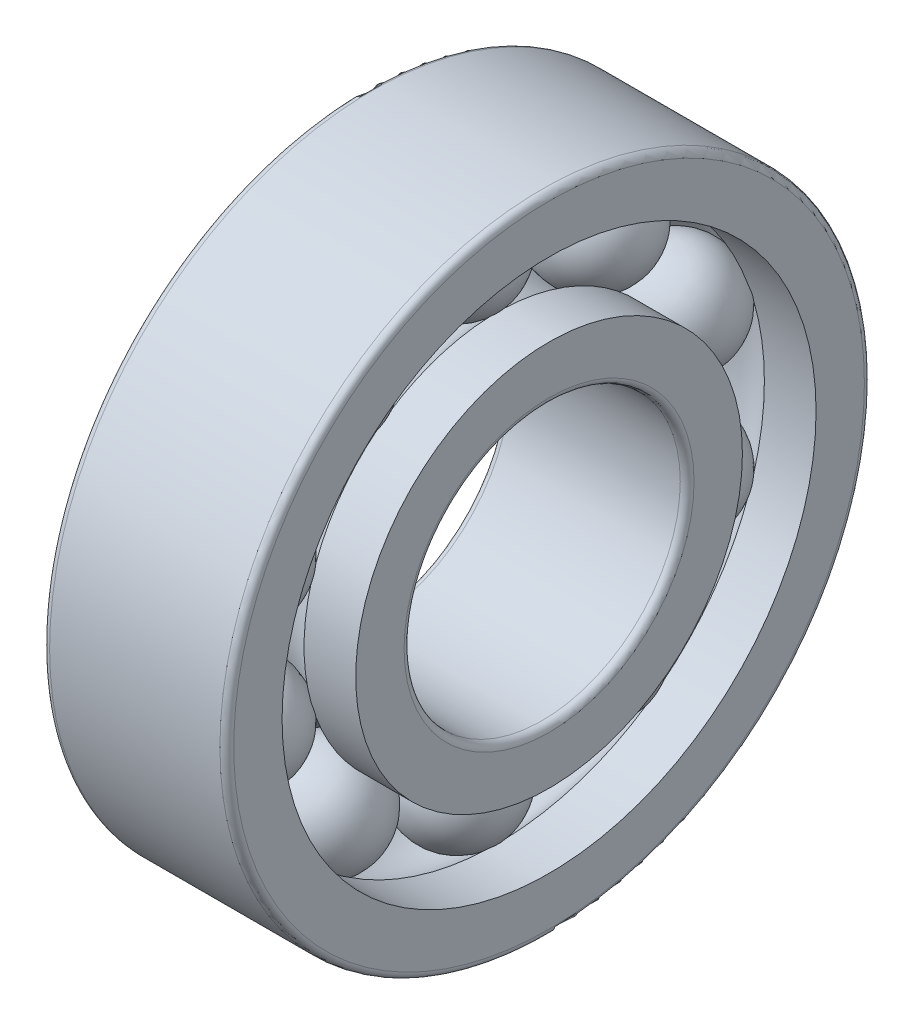
SolidWorks part; units mm, degrees
ref_plane "Plane1" through (0, 0, 0) normal (0, 0, 1) x (1, 0, 0)
ref_plane "Plane2" through (0, 0, 0) normal (0, 1, 0) x (1, 0, 0)
ref_plane "Plane3" through (0, 0, 0) normal (1, 0, 0) x (0, 0, -1)
sketch "Clipboard" plane through (0, 0, 0) normal (0, 0, 1) x (1, 0, 0)
  line L0 (-10, 0) -> (10, 0) construction
  line L1 (0, 0) -> (22.021, -3.8829)
  line L2 (0, 0) -> (9.8481, 1.7365)
  line L3 (0, 0) -> (22.021, -3.8829)
  line L4 (0, 0) -> (-22.3573, -0.3902)
  dimension "BallCLRad" = 10
sketch "CagSpiSke" plane through (0, 0, 0) normal (0, 0, 1) x (1, 0, 0)
  line L0 (0.24, 9.6) -> (0.24, 10.4)
  line L1 (0.24, 10.4) -> (-0.24, 10.4)
  line L2 (-0.24, 10.4) -> (-0.24, 9.6)
  line L3 (-0.24, 9.6) -> (0.24, 9.6)
  line L4 (-20.6375, 0) -> (20.6375, 0) construction
  line L5 (0, 0) -> (0, 23.7692) construction
  dimension "OD" = 20.8
  dimension "ID" = 19.2
revolve "CageSpine" add sketch "CagSpiSke" angle 0.001 about L4 reverse direction yes
ref_axis "Axis1" through (-50, 0, 0) along (1, 0, 0)
sketch "CagBalSke" plane through (0, 0, 0) normal (0, 0, 1) x (1, 0, 0)
  line L0 (-2.64, 10) -> (2.64, 10)
  line L1 (-1.905, 10) -> (1.905, 10) construction
  line L2 (-10, 0) -> (10, 0) construction
  line L3 (0, 0) -> (0, 24) construction
  arc A0 (2.64, 10) -> (-2.64, 10) centre (0, 10) cw
  dimension "BallCLRad" = 10
revolve "CageBall" [suppressed] add sketch "CagBalSke" angle 360 about L1 reverse direction yes
pattern_circular "CageBalls" [suppressed] count 10 every 36 about axis through (-50, 0, 0) along (1, 0, 0)
sketch "CagTrmODSke" plane through (0, 0, 0) normal (0, 0, 1) x (1, 0, 0)
  line L0 (2.641, 10.4) -> (2.641, 12.641)
  line L1 (2.641, 12.641) -> (-2.641, 12.641)
  line L2 (-2.641, 12.641) -> (-2.641, 10.4)
  line L3 (-2.641, 10.4) -> (2.641, 10.4)
  line L4 (-20.6375, 0) -> (20.6375, 0) construction
  line L5 (0, 0) -> (0, 25) construction
  dimension "Width" = 5.282
  dimension "ID" = 20.8
  dimension "OD" = 25.282
revolve "CageTrimOD" [suppressed] cut sketch "CagTrmODSke" angle 360 about L4 reverse direction yes
sketch "CagTrmIDSke" plane through (0, 0, 0) normal (0, 0, 1) x (1, 0, 0)
  line L0 (2.641, 7.361) -> (2.641, 9.6)
  line L1 (2.641, 9.6) -> (-2.641, 9.6)
  line L2 (-2.641, 9.6) -> (-2.641, 7.361)
  line L3 (-2.641, 7.361) -> (2.641, 7.361)
  line L4 (-20.6375, 0) -> (20.6375, 0) construction
  line L5 (0, 0) -> (0, 25) construction
  dimension "Width" = 5.282
  dimension "ID" = 14.722
  dimension "OD" = 19.2
revolve "CageTrimID" [suppressed] cut sketch "CagTrmIDSke" angle 360 about L4 reverse direction yes
sketch "BalSimSke" plane through (0, 0, 0) normal (0, 0, 1) x (1, 0, 0)
  line L0 (-10, 0) -> (10, 0) construction
  line L1 (-10, 10) -> (10, 10) construction
  line L2 (0, 0) -> (0, 23) construction
  circle A0 centre (0, 10) radius 2.4
  dimension "BallCLRad" = 10
  dimension "Ball_diameter" = 4.8
revolve "BallsSimplified" [suppressed] add sketch "BalSimSke" angle 360 about L0
sketch "BalDetSke" plane through (0, 0, 0) normal (0, 0, 1) x (1, 0, 0)
  line L0 (-2.4, 10) -> (2.4, 10)
  line L1 (-1.905, 10) -> (1.905, 10) construction
  line L2 (0, 0) -> (0, 25) construction
  arc A0 (2.4, 10) -> (-2.4, 10) centre (0, 10) cw
  dimension "BallCLRad" = 10
  dimension "Ball_diameter" = 4.8
revolve "BallDetailed" add sketch "BalDetSke" angle 360 about L1 reverse direction yes
sketch "InnRacSke" plane through (0, 0, 0) normal (0, 0, 1) x (1, 0, 0)
  line L0 (-1.7552, 8.4) -> (-4, 8.4)
  line L1 (-4, 8.4) -> (-4, 6.3)
  line L2 (-3.7, 6) -> (3.7, 6)
  line L3 (4, 6.3) -> (4, 8.4)
  line L4 (4, 8.4) -> (1.7552, 8.4)
  line L5 (-20.6375, 0) -> (20.6375, 0) construction
  line L6 (0, 0) -> (0, 30) construction
  arc A0 (-4, 6.3) -> (-3.7, 6) centre (-3.7, 6.3) ccw
  arc A1 (3.7, 6) -> (4, 6.3) centre (3.7, 6.3) ccw
  arc A2 (1.7552, 8.4) -> (-1.7552, 8.4) centre (0, 10) cw
  dimension "BallCLRad" = 10
  dimension "Fillet_radius" = 0.3
  dimension "Ball_diameter" = 4.75
  dimension "ID" = 12
  dimension "OD" = 16.8
  dimension "Width" = 8
revolve "InnerRace" add sketch "InnRacSke" angle 360 about L5 reverse direction yes
sketch "OutRacSke" plane through (0, 0, 0) normal (0, 0, 1) x (1, 0, 0)
  line L0 (-1.7552, 11.6) -> (-4, 11.6)
  line L1 (-4, 11.6) -> (-4, 13.7)
  line L2 (-3.7, 14) -> (3.7, 14)
  line L3 (4, 13.7) -> (4, 11.6)
  line L4 (4, 11.6) -> (1.7552, 11.6)
  line L5 (-20.6375, 0) -> (20.6375, 0) construction
  line L6 (0, 0) -> (0, 30) construction
  arc A0 (-4, 13.7) -> (-3.7, 14) centre (-3.7, 13.7) cw
  arc A1 (3.7, 14) -> (4, 13.7) centre (3.7, 13.7) cw
  arc A2 (1.7552, 11.6) -> (-1.7552, 11.6) centre (0, 10) ccw
  dimension "BallCLRad" = 10
  dimension "Fillet_radius" = 0.3
  dimension "Ball_diameter" = 4.75
  dimension "Width" = 8
revolve "OuterRace" add sketch "OutRacSke" angle 360 about L5 reverse direction yes
pattern_circular "BallsDetailed" count 10 every 36 about axis through (-50, 0, 0) along (1, 0, 0) of "BallDetailed"
equation "\"BallCLRad@Clipboard\" = ( \"OD@OutRacSke\" + \"ID@InnRacSke\" ) / 4"
equation "\"BallCLRad@BalSimSke\" = \"BallCLRad@Clipboard\""
equation "\"BallCLRad@BalDetSke\" = \"BallCLRad@Clipboard\""
equation "\"BallCLRad@InnRacSke\" = \"BallCLRad@Clipboard\""
equation "\"BallCLRad@OutRacSke\" = \"BallCLRad@Clipboard\""
equation "\"Ball_diameter@InnRacSke\" = \"Ball_diameter@BalDetSke\" - 0.05"
equation "\"Ball_diameter@OutRacSke\" = \"Ball_diameter@BalDetSke\" - 0.05"
equation "\"Ball_diameter@BalSimSke\" = \"Ball_diameter@BalDetSke\""
equation "\"Width@OutRacSke\" = \"Width@InnRacSke\""
equation "\"Fillet_radius@OutRacSke\" = \"Fillet_radius@InnRacSke\""
equation "\"Max_count@Clipboard\" = int( 3.14159265 / atn(( \"Ball_diameter@BalDetSke\" / 2) / sqr( \"BallCLRad@Clipboard\"  *  \"BallCLRad@Clipboard\" - ( \"Ball_diameter@BalDetSke\" / 2) *  ( \"Ball_diameter@BalDetSke\" / 2))))"
equation "\"Max_count@Clipboard\" = ((sgn( \"Max_count@Clipboard\" - \"Count@Clipboard\" )-1)*( \"Max_count@Clipboard\" - \"Count@Clipboard\" ))/-2+ \"Count@Clipboard\""
equation "\"Count@BallsDetailed\" = int( \"Show_count@Clipboard\" ) "
equation "\"Count@BallsDetailed\" = ((sgn( \"Count@BallsDetailed\" - \"Max_count@Clipboard\" )-1)*( \"Count@BallsDetailed\" - \"Max_count@Clipboard\" ))/-2+ \"Max_count@Clipboard\""
equation "\"Count@BallsDetailed\" = ((sgn( \"Count@BallsDetailed\" - \"Min_count@Clipboard\" )+1)*( \"Count@BallsDetailed\" - \"Min_count@Clipboard\"))/2 +\"Min_count@Clipboard\""
equation "\"Angle@BallsDetailed\" = 360.0 / \"Max_count@Clipboard\""
equation "\"BallCLRad@CagBalSke\" = \"BallCLRad@Clipboard\""
equation "\"Count@CageBalls\" = \"Count@BallsDetailed\""
equation "\"Angle@CageBalls\" = \"Angle@BallsDetailed\""
equation "\"Angle@CageSpine\" =  \"Angle@CageBalls\" * ( \"Count@CageBalls\" -1 + int( \"Count@CageBalls\" / \"Max_count@Clipboard\" ) )  + 0.001 -  int( \"Count@CageBalls\" / \"Max_count@Clipboard\" ) * 0.001"
equation "\"Angle@CageSpine\" =  \"Angle@CageSpine\" * int( \"Min_count@Clipboard\" / 2) + int(1 / \"Min_count@Clipboard\")  * 0.001"
equation "\"CageWallOD@CagBalSke\" =  \"Ball_diameter@BalDetSke\" * 1.1"
equation "\"Thickness@CagSpiSke\" =  \"Ball_diameter@BalDetSke\" * 0.1"
equation "\"OD@CagTrmODSke\" = \"BallCLRad@Clipboard\" * 2 + \"CageWallOD@CagBalSke\" + 0.002"
equation "\"ID@CagTrmODSke\" = \"BallCLRad@Clipboard\" * 2 + \"Ball_diameter@BalDetSke\" / 6"
equation "\"OD@CagTrmIDSke\" = \"BallCLRad@Clipboard\" * 2 - \"Ball_diameter@BalDetSke\" / 6"
equation "\"ID@CagTrmIDSke\" = \"BallCLRad@Clipboard\" * 2 - \"CageWallOD@CagBalSke\" + 0.002"
equation "\"OD@CagSpiSke\" = \"ID@CagTrmODSke\""
equation "\"ID@CagSpiSke\" = \"OD@CagTrmIDSke\""
equation "\"Width@CagTrmODSke\" = \"CageWallOD@CagBalSke\" + 0.002"
equation "\"Width@CagTrmIDSke\" = \"CageWallOD@CagBalSke\" + 0.002"
